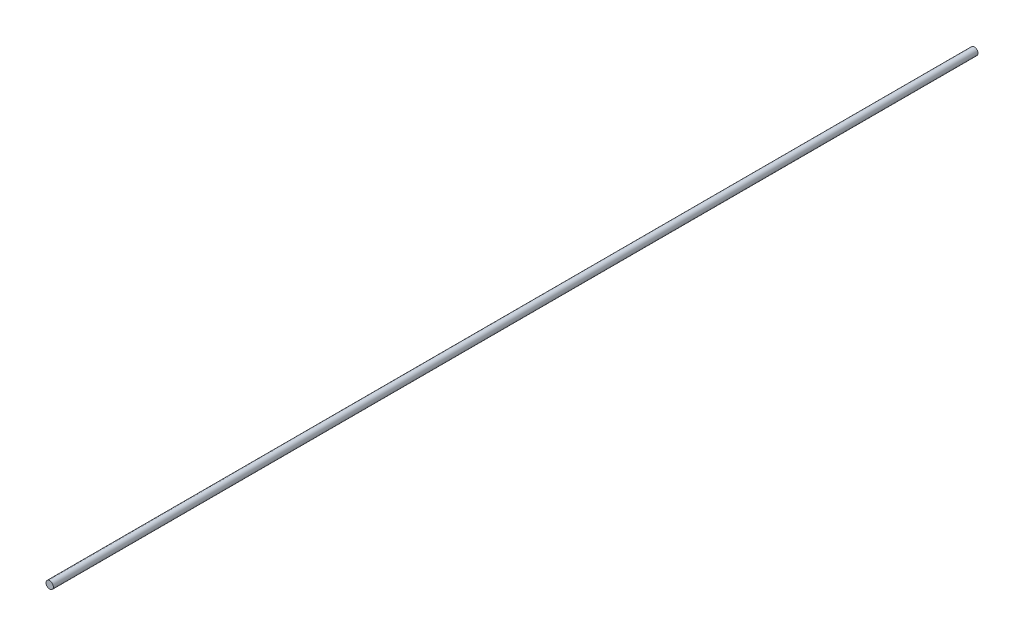
SolidWorks part; units mm, degrees
material "1.4000 (X6Cr13)"
ref_plane "Plan de face" through (0, 0, 0) normal (0, 0, 1) x (1, 0, 0)
ref_plane "Plan de dessus" through (0, 0, 0) normal (0, 1, 0) x (1, 0, 0)
ref_plane "Plan de droite" through (0, 0, 0) normal (1, 0, 0) x (0, 0, -1)
sketch "Esquisse1" plane through (0, 0, 0) normal (0, 0, 1) x (1, 0, 0)
  circle A0 centre (0, 0) radius 4
  dimension "D1" = 8
extrude "Boss.-Extru.1" add sketch "Esquisse1" along normal blind 1000
